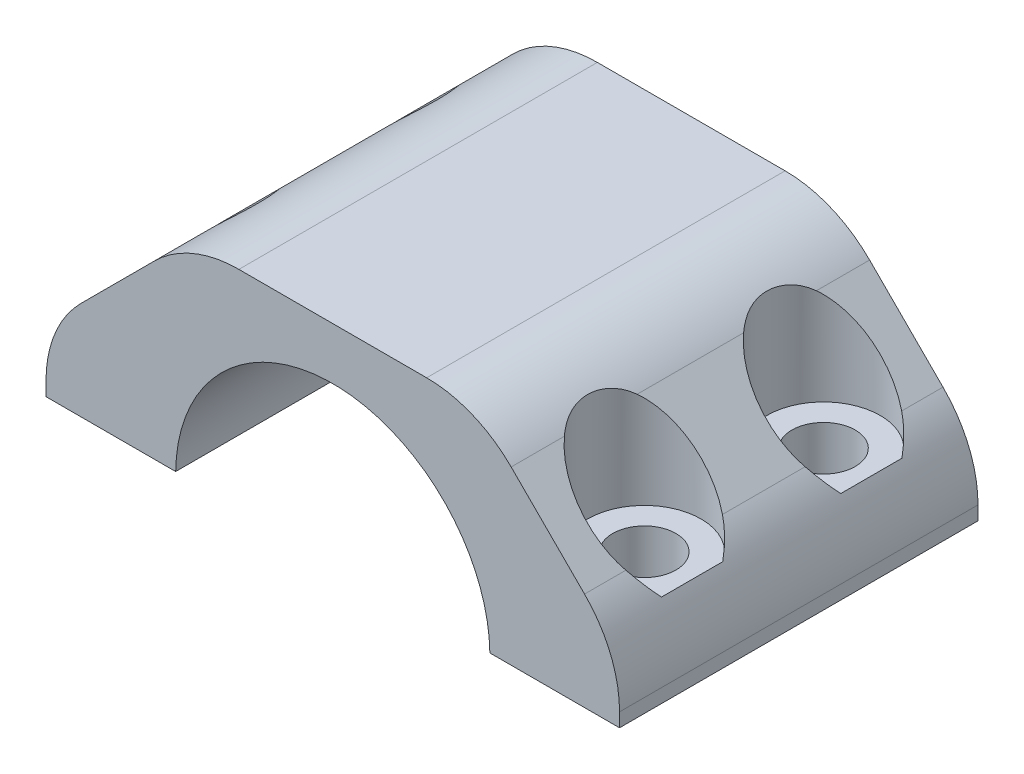
SolidWorks part; units mm, degrees
ref_plane "Front Plane" through (0, 0, 0) normal (0, 0, 1) x (1, 0, 0)
ref_plane "Top Plane" through (0, 0, 0) normal (0, 1, 0) x (1, 0, 0)
ref_plane "Right Plane" through (0, 0, 0) normal (1, 0, 0) x (0, 0, -1)
sketch "Sketch1" plane through (0, 0, 0) normal (0, 0, 1) x (1, 0, 0)
  line L1 (-24, -8.75) -> (24, -8.75)
  line L2 (-24, -8.75) -> (-24, 8.75)
  line L3 (-24, 8.75) -> (24, 8.75)
  line L4 (24, -8.75) -> (24, 8.75)
  line L5 (-24, -8.75) -> (24, 8.75) construction
  line L6 (-24, 8.75) -> (24, -8.75) construction
  point P0 (0, 0)
  dimension "D1" = 48
  dimension "D2" = 17.5
extrude "body" add sketch "Sketch1" along normal blind 30
sketch "Sketch2" plane through (0, 0, 0) normal (0, 0, 1) x (1, 0, 0)
  line L0 (0, -8.75) -> (0, 13.732) construction
  line L1 (-24, -8.75) -> (24, -8.75) construction
  line L2 (13.15, -8.75) -> (-13.15, -8.75)
  arc A0 (13.15, -8.75) -> (-13.15, -8.75) centre (0, -8.75) ccw
  dimension "D1" = 26.3
extrude "tube_cutout" cut sketch "Sketch2" along normal through all
sketch "Sketch3" plane through (0, -8.75, 0) normal (0, -1, 0) x (1, 0, 0)
  line L0 (18.575, 30) -> (18.575, 0) construction
  line L1 (13.15, 30) -> (24, 30) construction
  line L2 (13.15, 0) -> (24, 0) construction
  line L3 (0, 0) -> (0, 25.8019) construction
  circle A0 centre (18.575, 22.5) radius 2.65
  circle A1 centre (18.575, 7.5) radius 2.65
  circle A2 centre (-18.575, 7.5) radius 2.65
  circle A3 centre (-18.575, 22.5) radius 2.65
  dimension "D1" = 5.3
  dimension "D2" = 7.5
  dimension "D3" = 22.5
extrude "M5" cut sketch "Sketch3" against normal through all
sketch "Sketch4" plane through (0, 0, 0) normal (0, 0, 1) x (1, 0, 0)
  line L0 (-24, 8.75) -> (-24, -3.25)
  line L1 (-24, 8.75) -> (-24, -8.75) construction
  line L2 (-24, -3.25) -> (-12, 8.75)
  line L3 (24, 8.75) -> (-24, 8.75) construction
  line L4 (-12, 8.75) -> (-24, 8.75)
  line L5 (0, 0) -> (0, 12.9873) construction
  line L6 (-24, -8.75) -> (-13.15, -8.75) construction
  line L7 (24, -3.25) -> (12, 8.75)
  line L8 (24, 8.75) -> (24, -3.25)
  line L9 (12, 8.75) -> (24, 8.75)
  dimension "D1" = 12
  dimension "D2" = 5.5
extrude "slope" cut sketch "Sketch4" along normal through all
sketch "Sketch5" plane through (0, -8.75, 0) normal (0, -1, 0) x (1, 0, 0)
  line L0 (0, 0) -> (0, 28.2785) construction
  circle A7 centre (18.575, 22.5) radius 4.75
  circle A8 centre (18.575, 7.5) radius 4.75
  circle A9 centre (-18.575, 7.5) radius 4.75
  circle A10 centre (-18.575, 22.5) radius 4.75
  dimension "D1" = 9.5
extrude "bolt_head_cutout" cut sketch "Sketch5" against normal blind 23 from offset 6.5 offset against normal yes
fillet "fillet" radius 10 4 edges at (24, -3.25, 15) (12, 8.75, 15) (-24, -3.25, 15) (-12, 8.75, 15)
sketch "Sketch7" plane through (0, -8.75, 0) normal (0, -1, 0) x (1, 0, 0)
  line L1 (24, 0) -> (-24, 0)
  line L2 (24, 0) -> (24, 30)
  line L3 (24, 30) -> (-24, 30)
  line L4 (-24, 0) -> (-24, 30)
extrude "clearance" cut sketch "Sketch7" against normal blind 0.2
